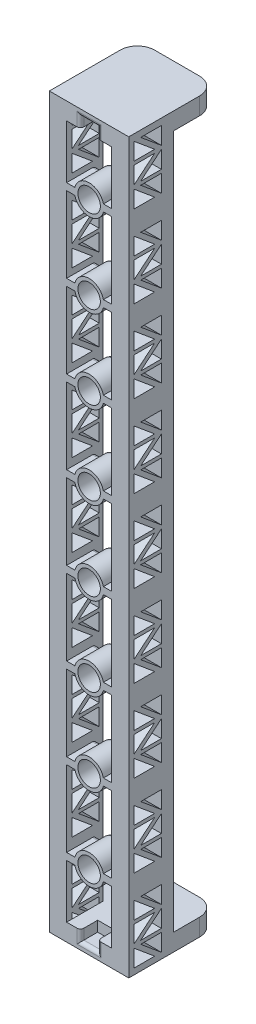
SolidWorks part; units mm, degrees
ref_plane "Front Plane" through (0, 0, 0) normal (0, 0, 1) x (1, 0, 0)
ref_plane "Top Plane" through (0, 0, 0) normal (0, 1, 0) x (1, 0, 0)
ref_plane "Right Plane" through (0, 0, 0) normal (1, 0, 0) x (0, 0, -1)
sketch "Sketch1" plane through (0, 0, 0) normal (0, 0, 1) x (1, 0, 0)
  line L0 (6.5, 100.5) -> (6.5, -100.5)
  line L1 (-11.5, 105.5) -> (11.5, 105.5)
  line L2 (-11.5, 105.5) -> (-11.5, -105.5)
  line L3 (-11.5, -105.5) -> (11.5, -105.5)
  line L4 (11.5, 105.5) -> (11.5, -105.5)
  line L5 (-11.5, 105.5) -> (11.5, -105.5) construction
  line L6 (-11.5, -105.5) -> (11.5, 105.5) construction
  line L7 (-6.5, -100.5) -> (6.5, -100.5)
  line L8 (-6.5, 100.5) -> (-6.5, -100.5)
  line L9 (-6.5, 100.5) -> (6.5, 100.5)
  point P0 (0, 0)
  dimension "D1" = 23
  dimension "D2" = 211
  dimension "D3" = 5
extrude "Boss-Extrude1" add sketch "Sketch1" along normal blind 13
sketch "Sketch7" plane through (0, 0, 13) normal (0, 0, 1) x (1, 0, 0)
  line L0 (0.0237, 87.6593) -> (0.0237, 80.2815) construction
  line L5 (-3.3958, 83) -> (-7.3958, 83)
  line L6 (7.4431, 85) -> (3.4431, 85)
  line L11 (-3.3958, 85) -> (-3.3958, 83)
  line L12 (-7.3958, 85) -> (-3.3958, 85)
  line L13 (3.4431, 85) -> (3.4431, 83)
  line L14 (3.4431, 83) -> (7.4431, 83)
  line L15 (7.4431, 83) -> (7.4431, 85)
  line L16 (-7.3958, 83) -> (-7.3958, 85)
  line L18 (11.5, 105.5) -> (-11.5, 105.5) construction
  circle A0 centre (0.0237, 84) radius 3.25
  circle A1 centre (0.0237, 84) radius 4.25
  point P5 (7.4431, 84)
  line M25 (-6.5, -100.5) -> (-6.5, 100.5)
  line M27 (6.5, 100.5) -> (6.5, -100.5)
  dimension "D1" = 6.5
  dimension "D2" = 8.5
  dimension "D3" = 20.5
  dimension "D4" = 4
  dimension "D5" = 2
extrude "Boss-Extrude5" add sketch "Sketch7" against normal blind 8.5 contours A1 L12 L5 M25 | L6 A1 L12 L11 L5 L14 L13 A0 | L12 A1 L5 L11 | L14 A1 L6 L13 | A1 L14 L6 M27 | L16 L5 L12 M25 | L14 L15 L6 M27 | L13 L14 L15 L6 region at (-3.2772, 84, 13) region at (-3.7921, 84, 13) region at (-5.3431, 84, 13) region at (-6.9479, 84, 13) region at (5.3668, 84, 13) region at (3.8394, 84, 13) region at (6.9715, 84, 13)
fillet "Fillet4" radius 1 6 edges at (-5.3035, 83, 4.5) (5.3272, 85, 4.5) (-5.3035, 85, 4.5) (0.0237, 88.25, 4.5) (5.3272, 83, 4.5) (0.0237, 79.75, 4.5)
pattern_linear "LPattern7" count 8 spacing 24 along (0, -1, 0) of "Boss-Extrude5", "Fillet4"
sketch "Sketch11" plane through (0, -105.5, 0) normal (0, -1, 0) x (-1, 0, 0)
  line L0 (6.5, -2.0313) -> (6.5, 0)
  line L2 (11.5, 0) -> (-11.5, 0) construction
  line L3 (11.5, -13) -> (11.5, 0) construction
  line L4 (8.5313, 0) -> (6.5, 0)
  line L5 (0, 0) -> (0, -13) construction
  line L6 (11.5, -13) -> (-11.5, -13) construction
  line L7 (-8.5313, 0) -> (-6.5, 0)
  line L8 (-6.5, -2.0313) -> (-6.5, 0)
  arc A0 (6.5, -2.0313) -> (8.5313, 0) centre (6.5, 0) ccw
  arc A1 (-6.5, -2.0313) -> (-8.5313, 0) centre (-6.5, 0) cw
  dimension "D1" = 5
ref_plane "Plane1" through (0, 0, 0) normal (-1, 0, 0) x (0, 0, 1)
ref_plane "Plane2" through (0, 0, 0) normal (0, 1, 0) x (1, 0, 0)
sketch "Sketch15" plane through (0, 105.5, 0) normal (0, 1, 0) x (1, 0, 0)
  line L0 (11.5, 0) -> (-11.5, 0)
  line L4 (11.5, 0) -> (4.4687, 0)
  line L5 (-11.5, 0) -> (-11.5, -13)
  line L6 (-11.5, -13) -> (11.5, -13)
  line L7 (11.5, -13) -> (11.5, 0)
  line L9 (-11.5, 0) -> (-11.5, -13)
  line L10 (-11.5, -13) -> (11.5, -13)
  line L11 (11.5, -13) -> (11.5, 0)
  line L21 (-6.5, 0) -> (-6.5, -2.0313)
  line L25 (-8.5313, 0) -> (-11.5, 0)
  line L26 (6.5, -2.0313) -> (6.5, 0)
  line L27 (6.5, 0) -> (-6.5, 0)
  arc A2 (-8.5313, 0) -> (-6.5, -2.0313) centre (-6.5, 0) ccw
  arc A6 (6.5, -2.0313) -> (4.4687, 0) centre (6.5, 0) ccw
  dimension "D1" = 0
extrude "Boss-Extrude8" add sketch "Sketch15" along normal blind 5
mirror "Mirror5" about plane through (0, 0, 0) normal (0, 1, 0) of "Boss-Extrude8"
sketch "Sketch19" plane through (-11.5, 0, 0) normal (-1, 0, 0) x (0, 0, 1)
  line L0 (13, 105.5) -> (0, 105.5) construction
  line L1 (13, 110.5) -> (13, -110.5) construction
  line L2 (0, 110.5) -> (0, -110.5) construction
  line L3 (0, 110.5) -> (13, 110.5) construction
  line L4 (13, 82.75) -> (0, 82.75) construction
  line L5 (13, 84.75) -> (0, 84.75) construction
  line L6 (0, 98.125) -> (13, 98.125) construction
  line L7 (9.5485, 103.625) -> (3.5485, 103.625)
  line L8 (3.5485, 103.625) -> (3.5485, 98.625)
  line L9 (3.5485, 98.625) -> (9.5485, 103.625)
  line L10 (11.5, 103.625) -> (11.5, 98.625)
  line L11 (11.5, 98.625) -> (5.5, 98.625)
  line L12 (5.5, 98.625) -> (11.5, 103.625)
  line L13 (0, 92.125) -> (13, 92.125) construction
  line L14 (0, 0) -> (13, 0) construction
  line L15 (11.5, 97.625) -> (5.5, 97.625)
  line L16 (11.5, 92.625) -> (11.5, 97.625)
  line L17 (5.5, 97.625) -> (11.5, 92.625)
  line L18 (3.5485, 92.625) -> (3.5485, 97.625)
  line L19 (9.5485, 92.625) -> (3.5485, 92.625)
  line L20 (3.5485, 97.625) -> (9.5485, 92.625)
  line L21 (11.5, 91.625) -> (11.5, 86.625)
  line L22 (5.5, 86.625) -> (11.5, 91.625)
  line L23 (11.5, 86.625) -> (5.5, 86.625)
  line L24 (9.5485, 91.625) -> (3.5485, 91.625)
  line L25 (3.5485, 86.625) -> (9.5485, 91.625)
  line L26 (3.5485, 91.625) -> (3.5485, 86.625)
  dimension "D1" = 5
  dimension "D2" = 5
  dimension "D3" = 2
  dimension "D4" = 1.2493
  dimension "D5" = 1.5
  dimension "D6" = 0.5
  dimension "D7" = 1.875
  dimension "D8" = 6
  dimension "D9" = 0.5
extrude "Cut-Extrude7" cut sketch "Sketch19" against normal blind 5
pattern_linear "LPattern10" count 9 spacing 23.8 along (0, -1, 0) of "Cut-Extrude7"
ref_plane "Plane3" through (0, 0, 0) normal (-1, 0, 0) x (0, 0, 1)
mirror "Mirror7" about plane through (0, 0, 0) normal (-1, 0, 0) of "LPattern10", "Cut-Extrude7"
sketch "Sketch22" plane through (0, 0, 0) normal (0, 0, -1) x (-1, 0, 0)
  line L0 (11.5, 110.5) -> (11.5, -110.5) construction
  line L1 (-11.5, 110.5) -> (11.5, 110.5)
  line L2 (-11.5, 110.5) -> (-11.5, 105.5)
  line L3 (-11.5, 105.5) -> (11.5, 105.5)
  line L4 (11.5, 110.5) -> (11.5, 105.5)
  line L6 (-11.5, -110.5) -> (11.5, -110.5)
  line L7 (-11.5, -110.5) -> (-11.5, -105.5)
  line L8 (-11.5, -105.5) -> (11.5, -105.5)
  line L9 (11.5, -110.5) -> (11.5, -105.5)
  dimension "D1" = 5
  dimension "D2" = 5
extrude "Cut-Extrude9" cut sketch "Sketch22" against normal through all
sketch "Sketch21" plane through (0, 0, 13) normal (0, 0, 1) x (1, 0, 0)
  line L1 (6.5, 100.5) -> (-6.5, 100.5) construction
  line L6 (-4.7323, 0) -> (3.9666, 0) construction
  line L11 (-2.5, 100.5) -> (2.5, 100.5)
  line L12 (-2.5, 100.5) -> (-2.5, 103.5)
  line L13 (-2.5, 103.5) -> (2.5, 103.5)
  line L14 (2.5, 100.5) -> (2.5, 103.5)
  line L15 (11.5, 105.5) -> (-11.5, 105.5) construction
  line L16 (-2.5, -103.5) -> (2.5, -103.5)
  line L17 (2.5, -100.5) -> (2.5, -103.5)
  line L18 (-2.5, -100.5) -> (2.5, -100.5)
  line L19 (-2.5, -100.5) -> (-2.5, -103.5)
  point P18 (0, 105.5)
  point P19 (0, 103.5)
  dimension "D3" = 3
  dimension "D4" = 5
extrude "Cut-Extrude8" cut sketch "Sketch21" against normal blind 5
fillet "Fillet7" radius 1 6 edges at (0, 103.5, 13) (2.5, -102, 13) (0, -103.5, 13) (-2.5, -102, 13) (2.5, 102, 13) (-2.5, 102, 13)
sketch "Sketch23" plane through (0, 0, 0) normal (0, 0, -1) x (-1, 0, 0)
  line L0 (11.5, 105.5) -> (11.5, -105.5) construction
  line L1 (-11.5, 105.5) -> (11.5, 105.5)
  line L2 (-11.5, 105.5) -> (-11.5, 100.5)
  line L3 (-11.5, 100.5) -> (11.5, 100.5)
  line L4 (11.5, 105.5) -> (11.5, 100.5)
  line L5 (-6.5, 100.5) -> (6.5, 100.5) construction
  line L6 (6.5, -100.5) -> (-6.5, -100.5) construction
  line L7 (-11.5, -105.5) -> (11.5, -105.5)
  line L8 (-11.5, -105.5) -> (-11.5, -100.5)
  line L9 (-11.5, -100.5) -> (11.5, -100.5)
  line L10 (11.5, -105.5) -> (11.5, -100.5)
extrude "Boss-Extrude9" add sketch "Sketch23" along normal blind 12.5
fillet "Fillet8" radius 5 4 edges at (11.5, 103, -12.5) (-11.5, 103, -12.5) (-11.5, -103, -12.5) (11.5, -103, -12.5)
sketch "Sketch25" plane through (0, -105.5, 0) normal (0, -1, 0) x (1, 0, 0)
  line L4 (-11.5, 13) -> (-11.5, -7.5) construction
  line L5 (-11.5, 13) -> (11.5, 13) construction
  line L6 (-9, -0.5) -> (-6, -0.5)
  line L7 (-6, -0.5) -> (-6, 2.5)
  line L8 (0, 2.725) -> (0, -1.8067) construction
  line L9 (6, -0.5) -> (6, 2.5)
  line L10 (9, -0.5) -> (6, -0.5)
  arc A0 (-6, 2.5) -> (-9, -0.5) centre (-6, -0.5) ccw
  arc A1 (6, 2.5) -> (9, -0.5) centre (6, -0.5) cw
  dimension "D1" = 13.5
  dimension "D2" = 5.5
  dimension "D3" = 3
extrude "Cut-Extrude11" cut sketch "Sketch25" against normal up to surface (206 mm away) from surface up to face at (0, 100.5, 4.4807) starting at face at (0, -100.5, 4.7607)
